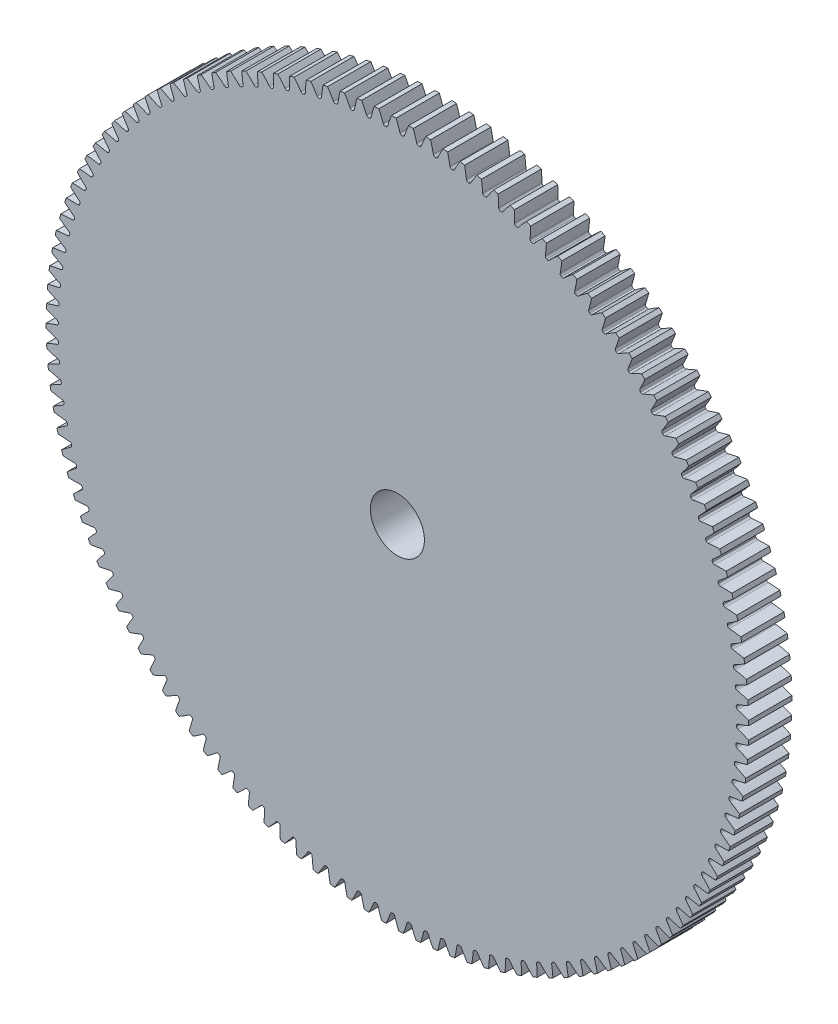
SolidWorks part; units mm, degrees
ref_plane "Front" through (0, 0, 0) normal (0, 0, 1) x (1, 0, 0)
ref_plane "Top" through (0, 0, 0) normal (0, 1, 0) x (1, 0, 0)
ref_plane "Right" through (0, 0, 0) normal (1, 0, 0) x (0, 0, -1)
sketch "Sketch3" plane through (0, 0, 0) normal (0, 0, 1) x (1, 0, 0)
  circle A0 centre (0, 0) radius 51.5938
  dimension "od" = 103.1875
extrude "gearBody" add sketch "Sketch3" along normal blind 6.35
sketch "Sketch2" plane through (0, 0, 0) normal (0, 0, 1) x (1, 0, 0)
  line L0 (0, 0) -> (44.1027, 18.2679) construction
  line L1 (60.0354, -8.954) -> (0, 0) construction
  line L2 (0, 0) -> (36.3143, 0) construction
  line L3 (50.7999, -0.1147) -> (50.7826, -1.3294) construction
  line L5 (50.7912, -0.722) -> (0, 0) construction
  line L7 (0, 0) -> (47.7364, 0) construction
  arc A0 (47.7268, -0.958) -> (47.7347, -0.399) centre (0, 0) ccw construction
  arc A1 (51.5934, 0.1942) -> (51.567, -1.6607) centre (0, 0) ccw construction
  arc A2 (50.7999, -0.1147) -> (50.7826, -1.3294) centre (0, 0) ccw construction
  arc A3 (49.7911, -0.7449) -> (49.7922, -0.6708) centre (0, 0) ccw
  arc A4 (60.0354, -8.954) -> (49.995, -1.0362) centre (43.5656, -19.5142) ccw
  arc A5 (60.0354, -8.954) -> (60.2656, 7.2438) centre (0, 0) ccw
  arc A6 (60.2656, 7.2438) -> (50.0042, -0.3853) centre (44.1027, 18.2679) cw
  arc A7 (49.7922, -0.6708) -> (50.0042, -0.3853) centre (50.0958, -0.6749) cw
  arc A8 (49.995, -1.0362) -> (49.7911, -0.7449) centre (50.0948, -0.7494) cw
  point P6 (60.2656, 7.2438)
  point P22 (60.0354, -8.954)
  dimension "baseDia" = 95.4728
  dimension "od" = 103.1875
  dimension "pd" = 101.6
  dimension "rd" = 99.5934
  dimension "rFillet" = 0.3037
  dimension "pointX" = 60.2656
  dimension "pointY" = 7.2438
  dimension "CTT" = 1.2148
  dimension "flankCenterAngle" = 22.5
extrude "toothCut" cut sketch "Sketch2" along normal through all
pattern_circular "CirPattern1" count 128 over 360 about axis through (0, 0, 0) along (0, 0, 1) of "toothCut"
sketch "hub1Dia" plane through (0, 0, 0) normal (0, 0, -1) x (-1, 0, 0)
  circle A0 centre (0, 0) radius 12.7
  dimension "hub1Dia" = 25.4
sketch "hub2Dia" plane through (0, 0, 6.35) normal (0, 0, 1) x (1, 0, 0)
  circle A0 centre (0, 0) radius 12.7
  dimension "hub2dia" = 25.4
sketch "boreDia" plane through (0, 0, 0) normal (0, 0, 1) x (1, 0, 0)
  circle A0 centre (0, 0) radius 1.5875
  dimension "boreDia" = 3.175
extrude "bore" cut sketch "boreDia" against normal mid plane 25400
sketch "Sketch4" plane through (0, 0, 0) normal (0, 0, -1) x (-1, 0, 0)
  point P0 (0, 0)
  arc B0 (-0.7937, -8.1656) -> (0, -11.1125) centre (2.9418, -8.7398) ccw
  arc B1 (-0.7937, -8.1656) -> (-1.303, -7.4562) centre (-1.4104, -8.0708) ccw
  arc B2 (-1.8918, -7.329) -> (-1.303, -7.4562) centre (0, 0) ccw
  arc B3 (-1.8918, -7.329) -> (-2.6485, -7.7648) centre (-2.0477, -7.9331) ccw
  arc B4 (-4.5881, -10.1211) -> (-2.6485, -7.7648) centre (-6.2878, -6.7454) ccw
  arc B5 (-4.7702, -6.6747) -> (-5.5563, -9.6237) centre (-1.8222, -9.0398) ccw
  arc B6 (-4.7702, -6.6747) -> (-4.8565, -5.8058) centre (-5.2568, -6.2843) ccw
  arc B7 (-5.3028, -5.4012) -> (-4.8565, -5.8058) centre (0, 0) ccw
  arc B8 (-5.3028, -5.4012) -> (-6.176, -5.4003) centre (-5.7399, -5.8464) ccw
  arc B9 (-9.034, -6.4711) -> (-6.176, -5.4003) centre (-8.8182, -2.6978) ccw
  arc B10 (-7.4685, -3.3954) -> (-9.6237, -5.5562) centre (-6.098, -6.9176) ccw
  arc B11 (-7.4685, -3.3954) -> (-7.1088, -2.5997) centre (-7.6947, -2.814) ccw
  arc B12 (-7.293, -2.0262) -> (-7.1088, -2.5997) centre (0, 0) ccw
  arc B13 (-7.293, -2.0262) -> (-8.0487, -1.5888) centre (-7.8941, -2.1932) ccw
  arc B14 (-11.0592, -1.0871) -> (-8.0487, -1.5888) centre (-8.9856, 2.0727) ccw
  arc B15 (-8.1656, 0.7937) -> (-11.1125, 0) centre (-8.7398, -2.9418) ccw
  arc B16 (-8.1656, 0.7937) -> (-7.4562, 1.303) centre (-8.0708, 1.4104) ccw
  arc B17 (-7.329, 1.8918) -> (-7.4562, 1.303) centre (0, 0) ccw
  arc B18 (-7.329, 1.8918) -> (-7.7648, 2.6485) centre (-7.9331, 2.0477) ccw
  arc B19 (-10.1211, 4.5881) -> (-7.7648, 2.6485) centre (-6.7454, 6.2878) ccw
  arc B20 (-6.6747, 4.7702) -> (-9.6237, 5.5563) centre (-9.0398, 1.8222) ccw
  arc B21 (-6.6747, 4.7702) -> (-5.8058, 4.8565) centre (-6.2843, 5.2568) ccw
  arc B22 (-5.4012, 5.3028) -> (-5.8058, 4.8565) centre (0, 0) ccw
  arc B23 (-5.4012, 5.3028) -> (-5.4003, 6.176) centre (-5.8464, 5.7399) ccw
  arc B24 (-6.4711, 9.034) -> (-5.4003, 6.176) centre (-2.6978, 8.8182) ccw
  arc B25 (-3.3954, 7.4685) -> (-5.5563, 9.6237) centre (-6.9176, 6.098) ccw
  arc B26 (-3.3954, 7.4685) -> (-2.5997, 7.1088) centre (-2.814, 7.6947) ccw
  arc B27 (-2.0262, 7.293) -> (-2.5997, 7.1088) centre (0, 0) ccw
  arc B28 (-2.0262, 7.293) -> (-1.5888, 8.0487) centre (-2.1932, 7.8941) ccw
  arc B29 (-1.0871, 11.0592) -> (-1.5888, 8.0487) centre (2.0727, 8.9856) ccw
  arc B30 (0.7937, 8.1656) -> (0, 11.1125) centre (-2.9418, 8.7398) ccw
  arc B31 (0.7937, 8.1656) -> (1.303, 7.4562) centre (1.4104, 8.0708) ccw
  arc B32 (1.8918, 7.329) -> (1.303, 7.4562) centre (0, 0) ccw
  arc B33 (1.8918, 7.329) -> (2.6485, 7.7648) centre (2.0477, 7.9331) ccw
  arc B34 (4.5881, 10.1211) -> (2.6485, 7.7648) centre (6.2878, 6.7454) ccw
  arc B35 (4.7702, 6.6747) -> (5.5562, 9.6237) centre (1.8222, 9.0398) ccw
  arc B36 (4.7702, 6.6747) -> (4.8565, 5.8058) centre (5.2568, 6.2843) ccw
  arc B37 (5.3028, 5.4012) -> (4.8565, 5.8058) centre (0, 0) ccw
  arc B38 (5.3028, 5.4012) -> (6.176, 5.4003) centre (5.7399, 5.8464) ccw
  arc B39 (9.034, 6.4711) -> (6.176, 5.4003) centre (8.8182, 2.6978) ccw
  arc B40 (7.4685, 3.3954) -> (9.6237, 5.5562) centre (6.098, 6.9176) ccw
  arc B41 (7.4685, 3.3954) -> (7.1088, 2.5997) centre (7.6947, 2.814) ccw
  arc B42 (7.293, 2.0262) -> (7.1088, 2.5997) centre (0, 0) ccw
  arc B43 (7.293, 2.0262) -> (8.0487, 1.5888) centre (7.8941, 2.1932) ccw
  arc B44 (11.0592, 1.0871) -> (8.0487, 1.5888) centre (8.9856, -2.0727) ccw
  arc B45 (8.1656, -0.7937) -> (11.1125, 0) centre (8.7398, 2.9418) ccw
  arc B46 (8.1656, -0.7937) -> (7.4562, -1.303) centre (8.0708, -1.4104) ccw
  arc B47 (7.329, -1.8918) -> (7.4562, -1.303) centre (0, 0) ccw
  arc B48 (7.329, -1.8918) -> (7.7648, -2.6485) centre (7.9331, -2.0477) ccw
  arc B49 (10.1211, -4.5881) -> (7.7648, -2.6485) centre (6.7454, -6.2878) ccw
  arc B50 (6.6747, -4.7702) -> (9.6237, -5.5563) centre (9.0398, -1.8222) ccw
  arc B51 (6.6747, -4.7702) -> (5.8058, -4.8565) centre (6.2843, -5.2568) ccw
  arc B52 (5.4012, -5.3028) -> (5.8058, -4.8565) centre (0, 0) ccw
  arc B53 (5.4012, -5.3028) -> (5.4003, -6.176) centre (5.8464, -5.7399) ccw
  arc B54 (6.4711, -9.034) -> (5.4003, -6.176) centre (2.6978, -8.8182) ccw
  arc B55 (3.3954, -7.4685) -> (5.5562, -9.6237) centre (6.9176, -6.098) ccw
  arc B56 (3.3954, -7.4685) -> (2.5997, -7.1088) centre (2.814, -7.6947) ccw
  arc B57 (2.0262, -7.293) -> (2.5997, -7.1088) centre (0, 0) ccw
  arc B58 (2.0262, -7.293) -> (1.5888, -8.0487) centre (2.1932, -7.8941) ccw
  arc B59 (1.0871, -11.0592) -> (1.5888, -8.0487) centre (-2.0727, -8.9856) ccw
  arc B60 (0, -11.1125) -> (1.0871, -11.0592) centre (0, 0) ccw
  arc B61 (9.6237, -5.5563) -> (10.1211, -4.5881) centre (0, 0) ccw
  arc B62 (11.1125, 0) -> (11.0592, 1.0871) centre (0, 0) ccw
  arc B63 (9.6237, 5.5562) -> (9.034, 6.4711) centre (0, 0) ccw
  arc B64 (5.5562, 9.6237) -> (4.5881, 10.1211) centre (0, 0) ccw
  arc B65 (0, 11.1125) -> (-1.0871, 11.0592) centre (0, 0) ccw
  arc B66 (-5.5563, 9.6237) -> (-6.4711, 9.034) centre (0, 0) ccw
  arc B67 (-9.6237, 5.5563) -> (-10.1211, 4.5881) centre (0, 0) ccw
  arc B68 (-11.1125, 0) -> (-11.0592, -1.0871) centre (0, 0) ccw
  arc B69 (-9.6237, -5.5562) -> (-9.034, -6.4711) centre (0, 0) ccw
  arc B70 (-5.5563, -9.6237) -> (-4.5881, -10.1211) centre (0, 0) ccw
  arc B71 (5.5562, -9.6237) -> (6.4711, -9.034) centre (0, 0) ccw
sketch_block_instance "Block1-1"
sketch_block "Block1"
extrude "Boss-Extrude1" add sketch "Sketch4" along normal blind 19.05
hole_wizard "5/16 (0.3125) Diameter Hole1" positions "Sketch6" profile "Sketch8" hole size "5/16" standard "ANSI Inch" end condition through all
sketch "Sketch6" plane through (0, 0, -19.05) normal (0, 0, -1) x (-1, 0, 0)
  point P0 (0, 0)
sketch "Sketch8" plane through (0, 0, -19.05) normal (1, 0, 0) x (0, 1, 0)
  line L0 (0, 0) -> (0, 25.4)
  line L1 (0, 25.4) -> (3.9687, 25.4)
  line L2 (3.9687, 25.4) -> (3.9687, 0)
  line L5 (3.9687, 0) -> (0, 0)
  line L11 (0, -6.35) -> (0, 107.95) construction
  dimension "Thru Hole Dia." = 7.9375
  dimension "Thru Hole Depth" = 25.4
